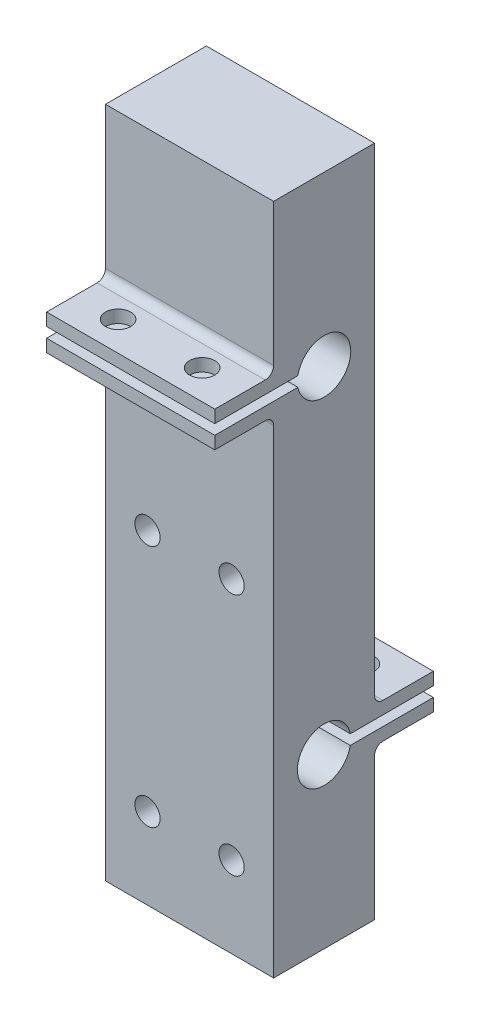
SolidWorks part; units mm, degrees
ref_plane "Front Plane" through (0, 0, 0) normal (0, 0, 1) x (1, 0, 0)
ref_plane "Top Plane" through (0, 0, 0) normal (0, 1, 0) x (1, 0, 0)
ref_plane "Right Plane" through (0, 0, 0) normal (1, 0, 0) x (0, 0, -1)
sketch "Sketch1" plane through (0, 0, 0) normal (0, 0, 1) x (1, 0, 0)
  line L1 (0, 0) -> (-20, 0)
  line L2 (0, 0) -> (0, 80)
  line L3 (0, 80) -> (-20, 80)
  line L4 (-20, 0) -> (-20, 80)
  dimension "D1" = 80
  dimension "D2" = 20
extrude "Boss-Extrude1" add sketch "Sketch1" along normal blind 12
sketch "Sketch3" plane through (0, 0, 0) normal (1, 0, 0) x (0, 0, -1)
  line L0 (-6, 80) -> (-6, 0) construction
  line L1 (-12, 80) -> (0, 80) construction
  line L2 (-12, 0) -> (0, 0) construction
  line L3 (-6, 0) -> (-12, 20) construction
  line L4 (-12, 0) -> (-12, 80) construction
  line L5 (-12, 20) -> (-6, 40) construction
  line L6 (-6, 40) -> (-12, 60) construction
  line L7 (-12, 60) -> (-6, 80) construction
  line L8 (-12, 60) -> (0, 60) construction
  line L9 (0, 0) -> (0, 80) construction
  line L10 (-12, 20) -> (0, 20) construction
  circle A0 centre (-6, 60) radius 3.175
  circle A1 centre (-6, 20) radius 3.175
  dimension "D1" = 6.35
extrude "Cut-Extrude1" cut sketch "Sketch3" against normal blind 12.7
sketch "Sketch6" plane through (0, 0, 0) normal (1, 0, 0) x (0, 0, -1)
  line L0 (-12, 62.1) -> (-12, 57.9)
  line L9 (-12, 57.9) -> (-19, 57.9)
  line L11 (-12, 62.1) -> (-19, 62.1)
  line L12 (-19, 57.9) -> (-19, 62.1)
  line L13 (-12, 60) -> (-19, 62.1) construction
  line L14 (-12, 60) -> (-19, 57.9) construction
  line L16 (7, 17.9) -> (0, 17.9)
  line L17 (7, 17.9) -> (7, 22.1)
  line L18 (7, 22.1) -> (0, 22.1)
  line L20 (7, 17.9) -> (0, 20) construction
  line L21 (7, 22.1) -> (0, 20) construction
  line L22 (0, 22.1) -> (0, 17.9)
  line L23 (0, 0) -> (0, 80) construction
  point P0 (-12, 60)
  point P2 (0, 20)
  dimension "D1" = 7
  dimension "D2" = 4.2
extrude "Boss-Extrude3" add sketch "Sketch6" against normal up to surface (20 mm away) up to face at (-20, 40, 6)
sketch "Sketch5" plane through (0, 0, 0) normal (1, 0, 0) x (0, 0, -1)
  line L0 (-12, 60) -> (0, 60) construction
  line L1 (-19, 59.4) -> (-9.1178, 59.4)
  line L3 (-19, 60.6) -> (-9.1178, 60.6)
  line L5 (-19, 62.1) -> (-19, 57.9) construction
  line L6 (-6, 20) -> (-2.825, 20) construction
  line L7 (-19, 60.6) -> (-19, 59.4)
  line L8 (7, 20.6) -> (7, 19.4)
  line L9 (7, 19.4) -> (-2.8822, 19.4)
  line L11 (7, 20.6) -> (-2.8822, 20.6)
  line L13 (-2.8822, 20.6) -> (-6, 20) construction
  line L14 (-6, 20) -> (-2.8822, 19.4) construction
  arc A0 (-9.1178, 59.4) -> (-9.1178, 60.6) centre (-6, 60) cw
  circle A1 centre (-6, 60) radius 3.175 construction
  arc A2 (-2.8822, 20.6) -> (-2.8822, 19.4) centre (-6, 20) cw
  circle A3 centre (-6, 20) radius 3.175 construction
  circle A4 centre (-6, 60) radius 3.175 construction
  circle A5 centre (-6, 60) radius 3.175 construction
  circle A6 centre (-6, 20) radius 3.175 construction
  point P0 (-12, 60)
  point P2 (0, 20)
  dimension "D2" = 1.2
extrude "Cut-Extrude2" cut sketch "Sketch5" against normal up to surface (20 mm away) up to face at (-20, 40, 6)
sketch "Sketch7" plane through (-20, 0, 0) normal (-1, 0, 0) x (0, 0, 1)
  line L0 (9.1178, 59.4) -> (9.2178, 59.4)
  line L1 (9.1178, 59.4) -> (19, 59.4) construction
  line L2 (9.2178, 59.4) -> (9.2178, 60.6)
  line L3 (19, 60.6) -> (9.1178, 60.6) construction
  line L4 (9.2178, 60.6) -> (9.1178, 60.6)
  line L5 (2.8822, 19.4) -> (2.7822, 19.4)
  line L6 (-7, 19.4) -> (2.8822, 19.4) construction
  line L7 (2.7822, 19.4) -> (2.7822, 20.6)
  line L8 (2.8822, 20.6) -> (-7, 20.6) construction
  line L9 (2.7822, 20.6) -> (2.8822, 20.6)
  arc A0 (9.1178, 59.4) -> (9.1178, 60.6) centre (6, 60) ccw construction
  arc A1 (9.1178, 59.4) -> (9.1178, 60.6) centre (6, 60) ccw
  arc A2 (2.8822, 20.6) -> (2.8822, 19.4) centre (6, 20) ccw construction
  arc A3 (2.8822, 20.6) -> (2.8822, 19.4) centre (6, 20) ccw
  dimension "D1" = 0.1
extrude "Boss-Extrude2" add sketch "Sketch7" against normal up to surface (7.3 mm away) up to face at (-12.7, 60, 6)
sketch "Sketch8" plane through (0, 62.1, 0) normal (0, 1, 0) x (1, 0, 0)
  line L0 (-20, -15.5) -> (0, -15.5) construction
  line L1 (-20, -19) -> (-20, -12) construction
  line L2 (0, -12) -> (0, -19) construction
  line L3 (-20, -15.5) -> (-15, -19) construction
  line L4 (-20, -19) -> (0, -19) construction
  line L5 (-15, -19) -> (-10, -15.5) construction
  line L6 (-10, -15.5) -> (-5, -19) construction
  line L7 (-5, -19) -> (0, -15.5) construction
  line L8 (-15, -19) -> (-15, -15.5) construction
  line L9 (-5, -19) -> (-5, -15.5) construction
  circle A0 centre (-15, -15.5) radius 1.5
  circle A1 centre (-5, -15.5) radius 1.5
  dimension "D1" = 3
extrude "Cut-Extrude3" cut sketch "Sketch8" against normal up to surface (4.2 mm away) up to face at (-10, 57.9, 15.5)
sketch "Sketch9" plane through (0, 22.1, 0) normal (0, 1, 0) x (1, 0, 0)
  line L0 (-20, 3.5) -> (0, 3.5) construction
  line L1 (-20, 0) -> (-20, 7) construction
  line L2 (0, 7) -> (0, 0) construction
  line L3 (-20, 3.5) -> (-15, 7) construction
  line L4 (-20, 7) -> (0, 7) construction
  line L5 (-15, 7) -> (-10, 3.5) construction
  line L6 (-10, 3.5) -> (-5, 7) construction
  line L7 (-5, 7) -> (0, 3.5) construction
  line L8 (-15, 7) -> (-15, 3.5) construction
  line L9 (-5, 7) -> (-5, 3.5) construction
  circle A0 centre (-15, 3.5) radius 1.5
  circle A1 centre (-5, 3.5) radius 1.5
  dimension "D1" = 3
extrude "Cut-Extrude4" cut sketch "Sketch9" against normal up to surface (4.2 mm away) up to face at (-10, 17.9, -3.5)
sketch "Sketch10" plane through (0, 0, 12) normal (0, 0, 1) x (1, 0, 0)
  line L0 (-20, 28.95) -> (0, 28.95) construction
  line L1 (-10, 0) -> (-20, 4.825) construction
  line L2 (-20, 4.825) -> (-10, 9.65) construction
  line L3 (-20, 57.9) -> (-20, 0) construction
  line L4 (0, 0) -> (0, 57.9) construction
  line L8 (-10, 28.95) -> (-10, 0) construction
  line L9 (-10, 9.65) -> (-20, 14.475) construction
  line L10 (-20, 0) -> (0, 0) construction
  line L11 (-20, 14.475) -> (-10, 19.3) construction
  line L12 (-10, 19.3) -> (-20, 24.125) construction
  line L13 (-20, 24.125) -> (-10, 28.95) construction
  line L14 (-20, 9.65) -> (0, 9.65) construction
  line L15 (-15, 9.65) -> (-10, 19.3) construction
  line L16 (-10, 19.3) -> (-5, 9.65) construction
  line L17 (-15, 9.65) -> (-20, 19.3) construction
  line L18 (-5, 9.65) -> (0, 19.3) construction
  line L19 (-20, 19.3) -> (0, 19.3) construction
  line L20 (-10, 28.95) -> (-10, 38.6) construction
  line L21 (-10, 38.6) -> (-20, 33.775) construction
  line L22 (-20, 33.775) -> (-10, 28.95) construction
  line L23 (-20, 38.6) -> (0, 38.6) construction
  line L24 (-20, 33.775) -> (0, 33.775) construction
  line L25 (-20, 24.125) -> (0, 24.125) construction
  circle A0 centre (-15, 9.65) radius 1.5
  circle A1 centre (-5, 9.65) radius 1.5
  circle A2 centre (-5, 38.6) radius 1.5
  circle A3 centre (-15, 38.6) radius 1.5
  dimension "D1" = 3
extrude "Cut-Extrude5" cut sketch "Sketch10" against normal up to surface (12 mm away) up to face at (-10, 51.05, 0)
sketch "Sketch11" plane through (0, 0, 0) normal (0, 0, -1) x (-1, 0, 0)
  circle A0 centre (5, 38.6) radius 2.75
  circle A1 centre (15, 38.6) radius 2.75
  circle A2 centre (5, 9.65) radius 2.75
  circle A3 centre (15, 9.65) radius 2.75
  dimension "D1" = 5.5
extrude "Cut-Extrude6" cut sketch "Sketch11" against normal blind 3.3
fillet "Fillet1" radius 1 4 edges at (-10, 57.9, 12) (-10, 62.1, 12) (-10, 17.9, 0) (-10, 22.1, 0)
